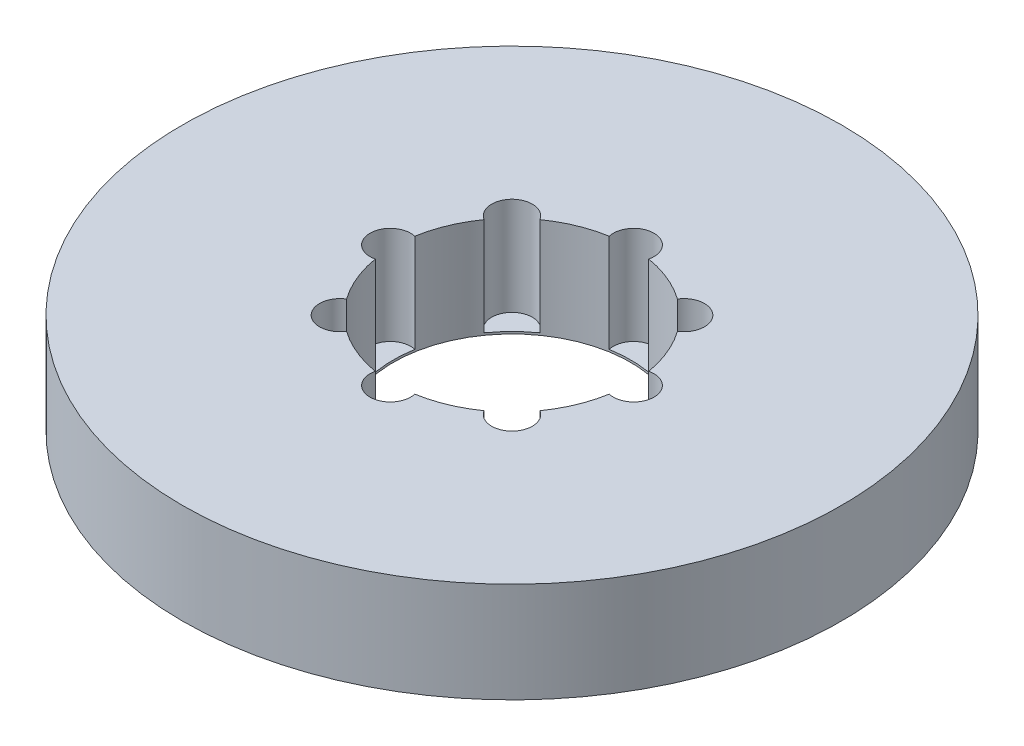
SolidWorks part; units mm, degrees
ref_plane "Front Plane" through (0, 0, 0) normal (0, 0, 1) x (1, 0, 0)
ref_plane "Top Plane" through (0, 0, 0) normal (0, 1, 0) x (1, 0, 0)
ref_plane "Right Plane" through (0, 0, 0) normal (1, 0, 0) x (0, 0, -1)
sketch "Sketch1" plane through (0, 0, 0) normal (0, 1, 0) x (1, 0, 0)
  circle A0 centre (0, 0) radius 62.5
  dimension "FLANGE_OD" = 125
extrude "Boss-Extrude1" add sketch "Sketch1" along normal blind 19
sketch "Sketch2" plane through (0, 0, 0) normal (0, 1, 0) x (1, 0, 0)
  circle A0 centre (0, 0) radius 22.5
  dimension "BORE_D" = 45
extrude "Cut-Extrude1" cut sketch "Sketch2" along normal through all
sketch "Sketch3" plane through (0, 19, 0) normal (0, 1, 0) x (1, 0, 0)
  circle A0 centre (0, 0) radius 23.0813 construction
  circle A1 centre (-23.0813, 0) radius 3.8516
  dimension "BOLT_D" = 7.7031
  dimension "BOLT_PCD" = 46.1626
extrude "Cut-Extrude2" cut sketch "Sketch3" against normal blind 18.5842
pattern_circular "CirPattern1" count 8 over 360 about axis through (0, 0, 0) along (0, 1, 0) of "Cut-Extrude2"
